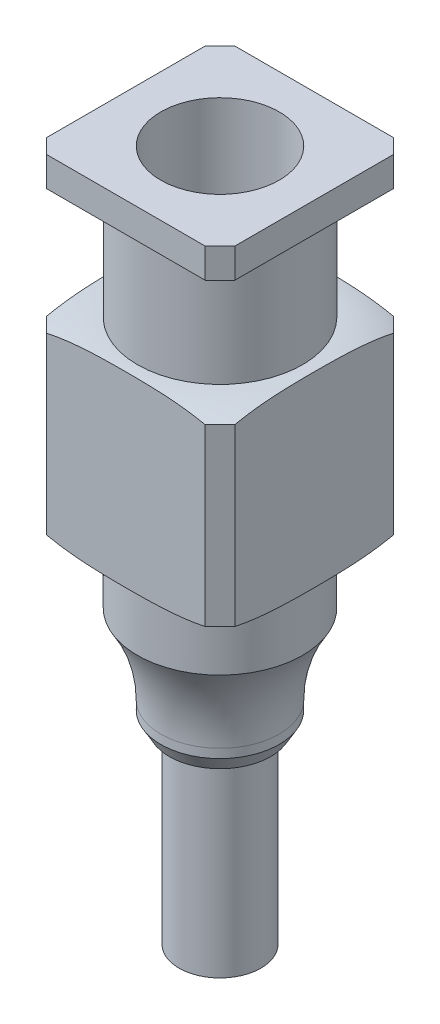
SolidWorks part; units mm, degrees
ref_plane "Front Plane" through (0, 0, 0) normal (0, 0, 1) x (1, 0, 0)
ref_plane "Top Plane" through (0, 0, 0) normal (0, 1, 0) x (1, 0, 0)
ref_plane "Right Plane" through (0, 0, 0) normal (1, 0, 0) x (0, 0, -1)
sketch "Sketch1" plane through (0, 0, 0) normal (0, 0, 1) x (1, 0, 0)
  line L0 (0, 0) -> (0, 23.35) construction
  line L1 (0, 0) -> (1.3843, 0)
  line L2 (1.3843, 0) -> (1.3843, 6.35)
  line L3 (1.3843, 6.35) -> (2, 6.35)
  line L4 (2, 6.35) -> (2, 9.85)
  line L5 (2.79, 9.85) -> (2.79, 23.35)
  line L6 (2.79, 23.35) -> (0, 23.35)
  line L7 (0, 0) -> (0, 23.35)
  line L8 (2, 9.85) -> (2.79, 9.85)
  dimension "D1" = 2.7686
  dimension "D2" = 6.35
  dimension "D3" = 5.58
  dimension "D4" = 4
  dimension "D5" = 3.5
  dimension "D6" = 17
revolve "Revolve1" add sketch "Sketch1" angle 360 about L0
fillet "Fillet1" radius 5 1 edges at (0, 9.85, -2)
chamfer "Chamfer2" distance 0.5 angle 30 1 edges at (0, 6.35, -2) first distance on face at (0, 7.1526, 2)
sketch "Sketch2" plane through (0, 0, 0) normal (0, 1, 0) x (1, 0, 0)
  line L0 (-3.175, 3.175) -> (3.175, -3.175) construction
  line L1 (-3.175, 3.175) -> (3.175, 3.175)
  line L2 (-3.175, 3.175) -> (-3.175, -3.175)
  line L3 (-3.175, -3.175) -> (3.175, -3.175)
  line L4 (3.175, 3.175) -> (3.175, -3.175)
  dimension "D1" = 6.35
extrude "Boss-Extrude1" add sketch "Sketch2" along normal blind 6.35 from offset 12
sketch "Sketch3" plane through (0, 0, 0) normal (0, 0, 1) x (1, 0, 0)
  line L0 (0, 23.35) -> (0, 0) construction
  line L1 (2.79, 23.35) -> (-2.79, 23.35) construction
  line L2 (-2.79, 18.35) -> (-2.79, 12) construction
  line L3 (-4.79, 17.85) -> (-4.79, 18.35)
  line L4 (-4.79, 18.35) -> (-2.79, 18.35)
  line L5 (-4.79, 12.5) -> (-4.79, 12)
  line L6 (-4.79, 12) -> (-2.79, 12)
  arc A0 (-2.79, 18.35) -> (-4.79, 17.85) centre (-2.79, 14.1) ccw
  arc A1 (-2.79, 12) -> (-4.79, 12.5) centre (-2.79, 16.25) cw
  dimension "D1" = 2
  dimension "D2" = 0.5
revolve "Cut-Revolve1" cut sketch "Sketch3" angle 360 about L0
chamfer "Chamfer1" distance 0.5 angle 45 4 edges at (-3.175, 15.175, -3.175) (3.175, 15.175, -3.175) (3.175, 15.175, 3.175) (-3.175, 15.175, 3.175)
sketch "Sketch4" plane through (0, 23.35, 0) normal (0, 1, 0) x (1, 0, 0)
  line L0 (-3.175, 2.675) -> (-3.175, -2.675) construction
  line L1 (-3.175, -2.675) -> (-2.675, -3.175) construction
  line L2 (-2.675, -3.175) -> (2.675, -3.175) construction
  line L3 (2.675, -3.175) -> (3.175, -2.675) construction
  line L4 (3.175, -2.675) -> (3.175, 2.675) construction
  line L5 (3.175, 2.675) -> (2.675, 3.175) construction
  line L6 (2.675, 3.175) -> (-2.675, 3.175) construction
  line L7 (-2.675, 3.175) -> (-3.175, 2.675) construction
  line L8 (-3.175, 2.675) -> (-3.175, -2.675)
  line L9 (-3.175, -2.675) -> (-2.675, -3.175)
  line L10 (-2.675, -3.175) -> (2.675, -3.175)
  line L11 (2.675, -3.175) -> (3.175, -2.675)
  line L12 (3.175, -2.675) -> (3.175, 2.675)
  line L13 (3.175, 2.675) -> (2.675, 3.175)
  line L14 (2.675, 3.175) -> (-2.675, 3.175)
  line L15 (-2.675, 3.175) -> (-3.175, 2.675)
extrude "Boss-Extrude3" add sketch "Sketch4" against normal blind 1
sketch "Sketch5" plane through (0, 23.35, 0) normal (0, 1, 0) x (1, 0, 0)
  circle A0 centre (0, 0) radius 2
  dimension "D1" = 4
extrude "Cut-Extrude1" cut sketch "Sketch5" against normal blind 11
sketch "Sketch6" plane through (0, 12.35, 0) normal (0, 1, 0) x (1, 0, 0)
  circle A0 centre (0, 0) radius 1.0795
  dimension "D1" = 2.159
extrude "Cut-Extrude2" cut sketch "Sketch6" against normal through all
chamfer "Chamfer3" distance 0.5 angle 45 1 edges at (0, 12.35, 1.0795)
sketch "Sketch7" plane through (0, 0, 0) normal (0, -1, 0) x (1, 0, 0)
  line L0 (0, 0.5397) -> (0, -0.5397) construction
  circle A0 centre (0, 0.5397) radius 0.5397
  circle A1 centre (0, -0.5397) radius 0.5397
  circle A2 centre (0, 0) radius 1.0795 construction
  circle A3 centre (-0.7197, 0) radius 0.3598
  dimension "D1" = 1.0795
  dimension "D2" = 0.7197
